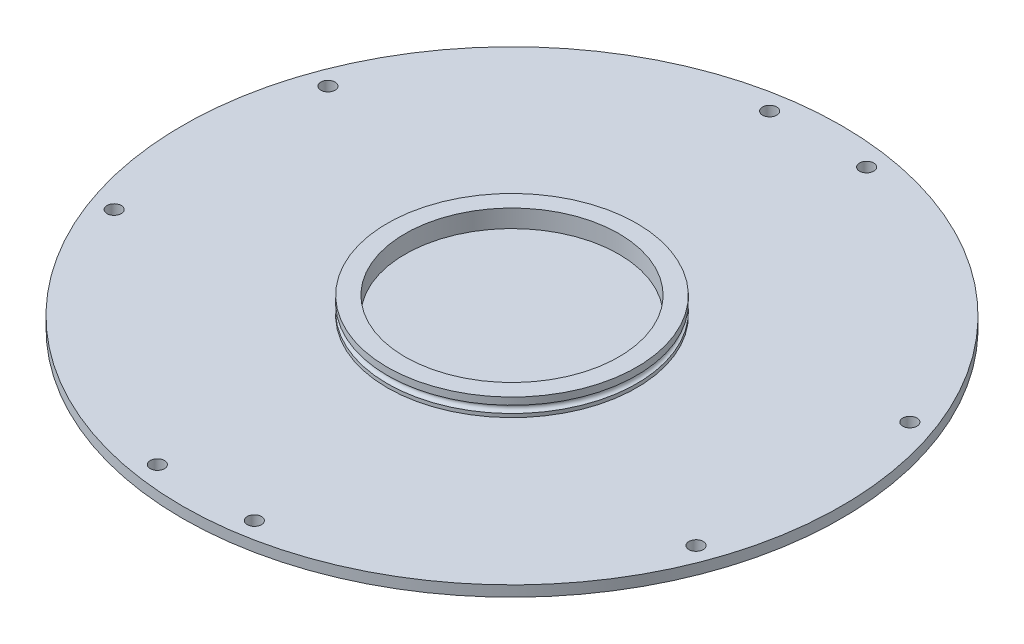
SolidWorks part; units mm, degrees
ref_plane "Front Plane" through (0, 0, 0) normal (0, 0, 1) x (1, 0, 0)
ref_plane "Top Plane" through (0, 0, 0) normal (0, 1, 0) x (1, 0, 0)
ref_plane "Right Plane" through (0, 0, 0) normal (1, 0, 0) x (0, 0, -1)
sketch "Sketch1" plane through (0, 0, 0) normal (0, 1, 0) x (1, 0, 0)
  line L0 (13.6098, 85.9289) -> (-13.6098, -85.9289) construction
  line L1 (13.6098, -85.9289) -> (-13.6098, 85.9289) construction
  line L2 (-81.6639, 30) -> (81.6639, 30) construction
  line L3 (81.6639, 30) -> (81.6639, -30) construction
  line L4 (81.6639, -30) -> (-81.6639, -30) construction
  line L5 (-81.6639, -30) -> (-81.6639, 30) construction
  circle A0 centre (0, 0) radius 92.5
  circle A1 centre (0, 0) radius 35
  circle A8 centre (0, 0) radius 30
  circle A11 centre (-81.6639, 30) radius 2
  circle A12 centre (81.6639, 30) radius 2
  circle A13 centre (13.6098, 85.9289) radius 2
  circle A14 centre (13.6098, -85.9289) radius 2
  circle A16 centre (-13.6098, 85.9289) radius 2
  circle A17 centre (-13.6098, -85.9289) radius 2
  circle A26 centre (81.6639, -30) radius 2
  circle A27 centre (-81.6639, -30) radius 2
  circle A28 centre (0, 0) radius 87 construction
  point P16 (0, 30)
  point P18 (0, 0)
  point P20 (0, 0)
  point P21 (0, 0)
  dimension "D1" = 185
  dimension "D2" = 70
  dimension "D3" = 18
  dimension "D6" = 5
  dimension "D7" = 60
  dimension "D4" = 4
  dimension "D5" = 174
extrude "Boss-Extrude1" add sketch "Sketch1" along normal blind 3 contours A1 | A0 A1 | A8 region at (-89.8837, 0, 0) region at (-34.0101, 0, 0)
extrude "Boss-Extrude2" add sketch "Sketch1<3>" along normal blind 5 from offset 3 contours A1 region at (-34.0101, 0, 0)
sketch "Sketch1<3>" plane through (0, 0, 0) normal (0, 1, 0) x (1, 0, 0) same geometry as "Sketch1"
sketch "Sketch2" plane through (0, 0, 0) normal (0, 0, 1) x (1, 0, 0)
  line L0 (35, 3) -> (35, 8) construction
  line L6 (35, 6) -> (35, 4)
  line L7 (0, 0) -> (0, 8) construction
  line L8 (35, 8) -> (-35, 8) construction
  line L9 (92.5, 3) -> (-92.5, 3) construction
  arc A0 (35, 6) -> (35, 4) centre (35, 5) ccw
  dimension "D1" = 2
  dimension "D2" = 1
revolve "Cut-Revolve1" cut sketch "Sketch2" angle 360 about L7
